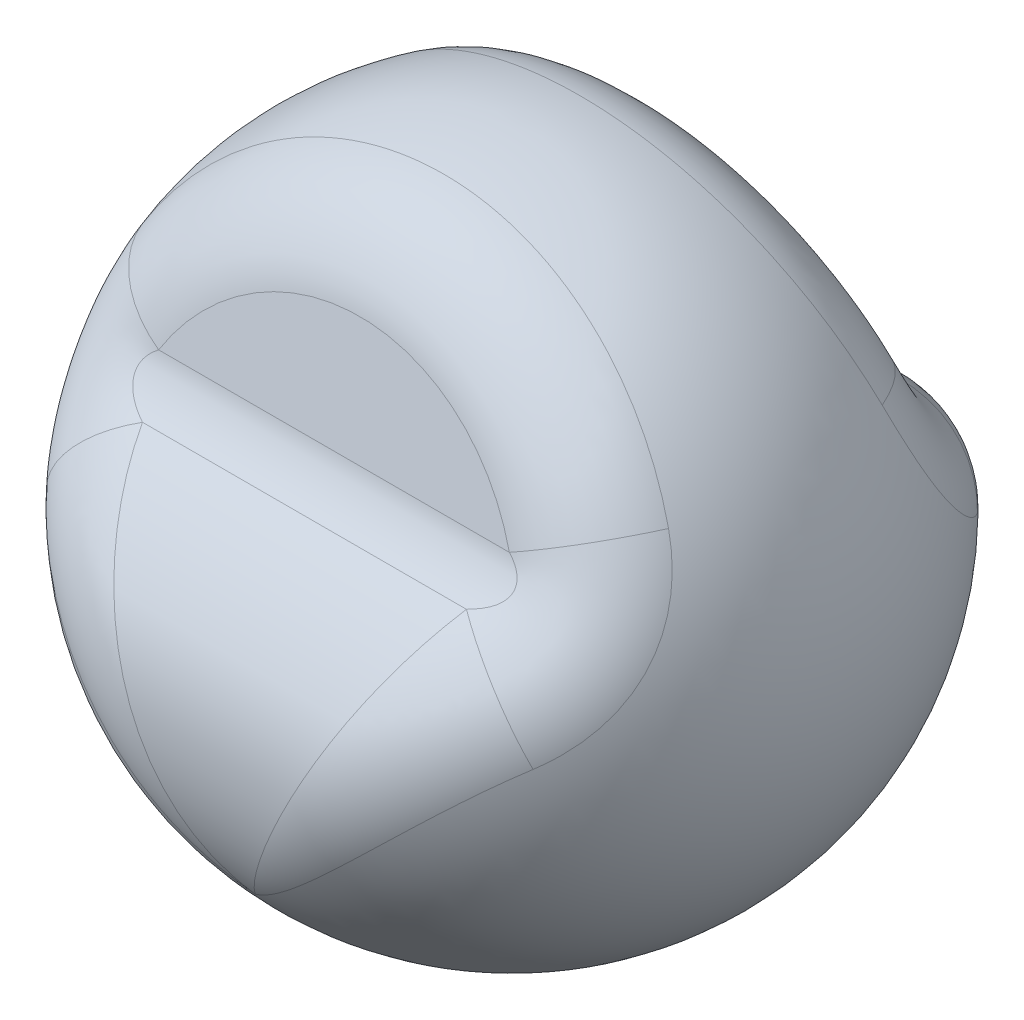
SolidWorks part; units mm, degrees
material "Polyester Resin"
ref_plane "Front Plane" through (0, 0, 0) normal (0, 0, 1) x (1, 0, 0)
ref_plane "Top Plane" through (0, 0, 0) normal (0, 1, 0) x (1, 0, 0)
ref_plane "Right Plane" through (0, 0, 0) normal (1, 0, 0) x (0, 0, -1)
sketch "Sketch1" plane through (0, 0, 0) normal (0, 0, 1) x (1, 0, 0)
  line L0 (0, -55) -> (0, 55) construction
  line L1 (55, 0) -> (-55, 0) construction
  line L2 (0, 15.2) -> (0, -15.2)
  arc A0 (0, 15.2) -> (0, -15.2) centre (0, 0) cw
  dimension "D1" = 15.2
revolve "Revolve1" add sketch "Sketch1" angle 360 about L2
sketch "Sketch2" plane through (0, 0, 0) normal (0, 0, 1) x (1, 0, 0)
  line L0 (0, -16.72) -> (0, 16.72) construction
  line L1 (-15.2, -13.42) -> (15.2, -13.42)
  line L2 (-15.2, -13.42) -> (-15.2, -20.024)
  line L3 (-15.2, -20.024) -> (15.2, -20.024)
  line L4 (15.2, -13.42) -> (15.2, -20.024)
  line L5 (-15.2, -13.42) -> (15.2, -20.024) construction
  line L6 (-15.2, -20.024) -> (15.2, -13.42) construction
  circle A0 centre (0, 0) radius 15.2 construction
  point P0 (0, -16.722)
  dimension "D2" = 28.62
  dimension "D1" = 30.4
  dimension "D3" = 6.604
extrude "Cut-Extrude1" cut sketch "Sketch2" against normal up to next and the other way up to next
sketch "Sketch3" plane through (0, 0, 0) normal (1, 0, 0) x (0, 0, -1)
  line L0 (-8.21, 6.35) -> (-6.35, 13.8101)
  line L1 (0, 15.741) -> (0, -15.741) construction
  line L2 (0, 0) -> (0, 19.5105) construction
  line L3 (16.72, 0) -> (-16.72, 0) construction
  line L4 (8.21, 6.35) -> (6.35, 13.8101)
  arc A0 (-11.8336, -9.5397) -> (-9.5726, 4.4482) centre (-4.4181, -3.5617) cw
  arc A1 (7.1375, -13.42) -> (-7.1375, -13.42) centre (0, 0) ccw construction
  arc A2 (-6.35, 13.8101) -> (-11.8336, -9.5397) centre (0, 0) ccw
  arc A3 (-9.5726, 4.4482) -> (-8.21, 6.35) centre (-11.2907, 7.1181) ccw
  arc A4 (11.8336, -9.5397) -> (9.5726, 4.4482) centre (4.4181, -3.5617) ccw
  arc A5 (9.5726, 4.4482) -> (8.21, 6.35) centre (11.2907, 7.1181) cw
  arc A6 (6.35, 13.8101) -> (11.8336, -9.5397) centre (0, 0) cw
  dimension "D3" = 3.175
  dimension "D4" = 9.525
  dimension "D1" = 14
  dimension "D2" = 6.35
  dimension "D5" = 6.35
extrude "Cut-Extrude2" cut sketch "Sketch3" against normal up to next and the other way up to next
fillet "Fillet1" radius 5.08 10 edges at (-5.9883, -2.0404, -13.8209) (-11.2935, 5.4876, -8.5663) (0, 13.8101, -6.35) (11.2935, 5.4876, -8.5663) (5.9883, -2.0404, -13.8209) (5.9883, -2.0404, 13.8209) (11.2622, 5.0878, 8.8496) (0, 13.8101, 6.35) (-11.2622, 5.0878, 8.8496) (-5.9883, -2.0404, 13.8209)
sketch "Sketch4" plane through (0, -13.42, 0) normal (0, -1, 0) x (1, 0, 0)
  circle A0 centre (0, 0) radius 2.3813
  dimension "D1" = 4.7625
extrude "Cut-Extrude3" cut sketch "Sketch4" against normal blind 20
